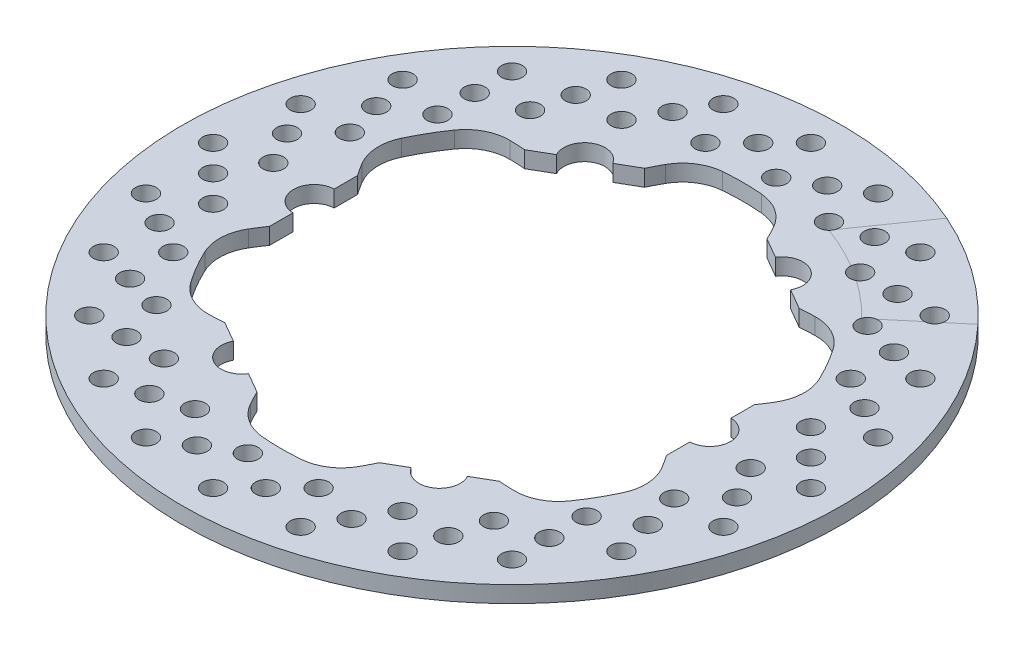
SolidWorks part; units mm, degrees
material "AISI 4130 Steel, annealed at 865C"
ref_plane "X-Y Datum" through (0, 0, 0) normal (0, 0, 1) x (1, 0, 0)
ref_plane "X-Z Datum" through (0, 0, 0) normal (0, 1, 0) x (1, 0, 0)
ref_plane "Y-Z Datum" through (0, 0, 0) normal (1, 0, 0) x (0, 0, -1)
ref_axis "Wheel Axis" through (0, 83.3456, 0) along (0, -1, 0)
sketch "Sketch1" plane through (0, 0, 0) normal (0, 1, 0) x (1, 0, 0)
  circle A0 centre (0, 0) radius 66.675
  circle A1 centre (0, 0) radius 95.25
  dimension "D1" = 133.35
  dimension "D2" = 190.5
extrude "Boss-Extrude2" add sketch "Sketch1" along normal mid plane 4.7625
sketch "Sketch2" plane through (0, -2.3813, 0) normal (0, -1, 0) x (1, 0, 0)
  line L0 (-25.358, 111.718) -> (41.2469, 45.1131) construction
  line L1 (0, 0) -> (0, 50000) construction
  circle A0 centre (0, 86.36) radius 3
  circle A1 centre (7.62, 78.74) radius 3
  circle A2 centre (15.24, 71.12) radius 3
  circle A3 centre (27.7398, 74.0848) radius 3
  circle A4 centre (33.1279, 64.7522) radius 3
  circle A5 centre (22.3516, 83.4174) radius 3
  circle A6 centre (45.9691, 64.3808) radius 3
  circle A7 centre (48.7582, 53.9717) radius 3
  circle A8 centre (43.18, 74.79) radius 3
  circle A9 centre (61.0657, 50.2894) radius 3
  circle A10 centre (61.0657, 39.5131) radius 3
  circle A11 centre (61.0657, 61.0657) radius 3
  circle A12 centre (72.0008, 32.7709) radius 3
  circle A13 centre (69.2117, 22.3618) radius 3
  circle A14 centre (74.79, 43.18) radius 3
  circle A15 centre (78.0292, 13.0191) radius 3
  circle A16 centre (72.641, 3.6865) radius 3
  circle A17 centre (83.4174, 22.3516) radius 3
  circle A18 centre (78.74, -7.62) radius 3
  circle A19 centre (71.12, -15.24) radius 3
  circle A20 centre (86.36, 0) radius 3
  circle A21 centre (74.0848, -27.7398) radius 3
  circle A22 centre (64.7522, -33.1279) radius 3
  circle A23 centre (83.4174, -22.3516) radius 3
  circle A24 centre (64.3808, -45.9691) radius 3
  circle A25 centre (53.9717, -48.7582) radius 3
  circle A26 centre (74.79, -43.18) radius 3
  circle A27 centre (50.2894, -61.0657) radius 3
  circle A28 centre (39.5131, -61.0657) radius 3
  circle A29 centre (61.0657, -61.0657) radius 3
  circle A30 centre (32.7709, -72.0008) radius 3
  circle A31 centre (22.3618, -69.2117) radius 3
  circle A32 centre (43.18, -74.79) radius 3
  circle A33 centre (13.0191, -78.0292) radius 3
  circle A34 centre (3.6865, -72.641) radius 3
  circle A35 centre (22.3516, -83.4174) radius 3
  circle A36 centre (-7.62, -78.74) radius 3
  circle A37 centre (-15.24, -71.12) radius 3
  circle A38 centre (0, -86.36) radius 3
  circle A39 centre (-27.7398, -74.0848) radius 3
  circle A40 centre (-33.1279, -64.7522) radius 3
  circle A41 centre (-22.3516, -83.4174) radius 3
  circle A42 centre (-45.9691, -64.3808) radius 3
  circle A43 centre (-48.7582, -53.9717) radius 3
  circle A44 centre (-43.18, -74.79) radius 3
  circle A45 centre (-61.0657, -50.2894) radius 3
  circle A46 centre (-61.0657, -39.5131) radius 3
  circle A47 centre (-61.0657, -61.0657) radius 3
  circle A48 centre (-72.0008, -32.7709) radius 3
  circle A49 centre (-69.2117, -22.3618) radius 3
  circle A50 centre (-74.79, -43.18) radius 3
  circle A51 centre (-78.0292, -13.0191) radius 3
  circle A52 centre (-72.641, -3.6865) radius 3
  circle A53 centre (-83.4174, -22.3516) radius 3
  circle A54 centre (-78.74, 7.62) radius 3
  circle A55 centre (-71.12, 15.24) radius 3
  circle A56 centre (-86.36, 0) radius 3
  circle A57 centre (-74.0848, 27.7398) radius 3
  circle A58 centre (-64.7522, 33.1279) radius 3
  circle A59 centre (-83.4174, 22.3516) radius 3
  circle A60 centre (-64.3808, 45.9691) radius 3
  circle A61 centre (-53.9717, 48.7582) radius 3
  circle A62 centre (-74.79, 43.18) radius 3
  circle A63 centre (-50.2894, 61.0657) radius 3
  circle A64 centre (-39.5131, 61.0657) radius 3
  circle A65 centre (-61.0657, 61.0657) radius 3
  circle A66 centre (-32.7709, 72.0008) radius 3
  circle A67 centre (-22.3618, 69.2117) radius 3
  circle A68 centre (-43.18, 74.79) radius 3
  circle A69 centre (-13.0191, 78.0292) radius 3
  circle A70 centre (-3.6865, 72.641) radius 3
  circle A71 centre (-22.3516, 83.4174) radius 3
  point P152 (0, 0)
  dimension "D1" = 6
  dimension "D2" = 7.62
  dimension "D3" = 7.62
  dimension "D4" = 78.74
  dimension "D5" = 86.36
  dimension "D6" = 7.62
  dimension "D7" = 24
extrude "Cut-Extrude1" cut sketch "Sketch2" against normal through all
sketch "Sketch3" plane through (0, 0, 0) normal (0, 1, 0) x (1, 0, 0)
  line L0 (-145.6254, 0) -> (145.6254, 0) construction
  line L1 (0, 0) -> (0, -50000) construction
  line L2 (-57.15, 13.1324) -> (-57.15, -13.1324) construction
  line L3 (-57.3278, 5.9505) -> (-57.3278, 12.7)
  line L4 (-57.3278, -5.9505) -> (-57.3278, -12.7)
  arc A0 (-57.3278, 5.9505) -> (-57.3278, -5.9505) centre (-57.15, 0) ccw
  arc A1 (-57.3278, 12.7) -> (-62.8618, 22.225) centre (1.2149, 53.0832) cw
  circle A2 centre (0, 0) radius 66.675 construction
  arc A3 (-57.3278, -12.7) -> (-62.8618, -22.225) centre (1.2149, -53.0832) ccw
  arc A4 (-62.8618, 22.225) -> (-62.8618, -22.225) centre (0, 0) ccw
  point P4 (0, 0)
  point P10 (-57.15, 0)
  dimension "D2" = 11.9062
  dimension "D5" = 71.12
  dimension "D1" = 57.15
  dimension "D3" = 0.3556
  dimension "D4" = 44.45
  dimension "D6" = 25.4
extrude "Boss-Extrude3" add sketch "Sketch3" along normal mid plane 4.7625
fillet "Fillet1" radius 12.7 2 edges at (-62.8618, 0, 22.225) (-62.8618, 0, -22.225)
pattern_circular "CirPattern1" count 6 over 360 about axis through (0, 83.3456, 0) along (0, -1, 0) of "Boss-Extrude3", "Fillet1"
sketch "Sketch4" plane through (0, 2.3813, 0) normal (0, 1, 0) x (1, 0, 0)
  line L0 (0, 0) -> (0, 49.634) construction
  line L1 (-1.648, -4.5278) -> (37.4871, 102.995) construction
  line L2 (38.4484, 87.1452) -> (24.4331, 67.1293)
  line L3 (51.2487, 49.7683) -> (69.5263, 65.105)
  circle A0 centre (0, 0) radius 71.4375 construction
  circle A1 centre (0, 0) radius 95.25 construction
  arc A2 (24.4331, 67.1293) -> (51.2487, 49.7683) centre (0, 0) cw
  arc A3 (38.4484, 87.1452) -> (69.5263, 65.105) centre (0, 0) cw
  dimension "D2" = 23.8125
  dimension "D1" = 20
  dimension "D3" = 15
  dimension "D4" = 15
  dimension "D5" = 38.1
split line "Split Line1"
